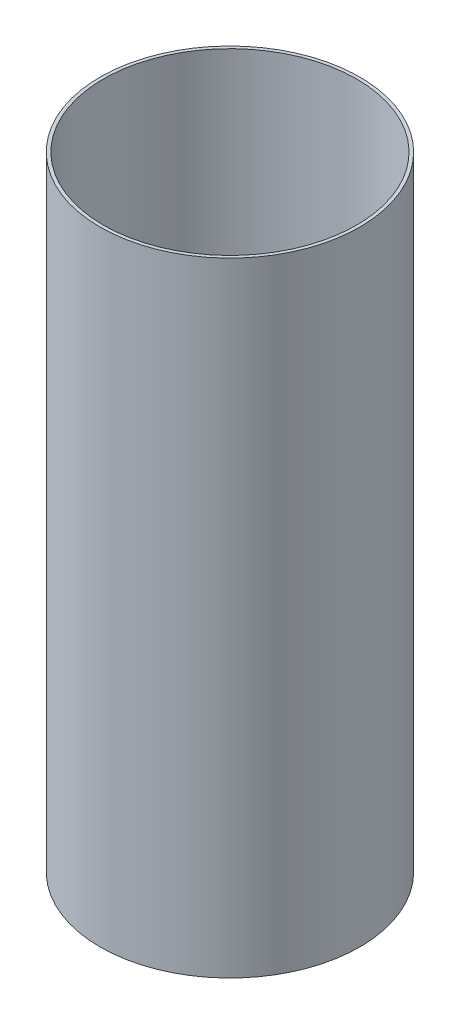
SolidWorks part; units mm, degrees
ref_plane "Front" through (0, 0, 0) normal (0, 0, 1) x (1, 0, 0)
ref_plane "Top" through (0, 0, 0) normal (0, 1, 0) x (1, 0, 0)
ref_plane "Right" through (0, 0, 0) normal (1, 0, 0) x (0, 0, -1)
sketch "Sketch1" plane through (0, 0, 0) normal (0, 1, 0) x (1, 0, 0)
  circle A0 centre (0, 0) radius 127
  circle A1 centre (0, 0) radius 123.825
  dimension "D1" = 254
  dimension "D2" = 3.175
extrude "Boss-Extrude1" add sketch "Sketch1" along normal blind 304.8 and the other way blind 304.8
